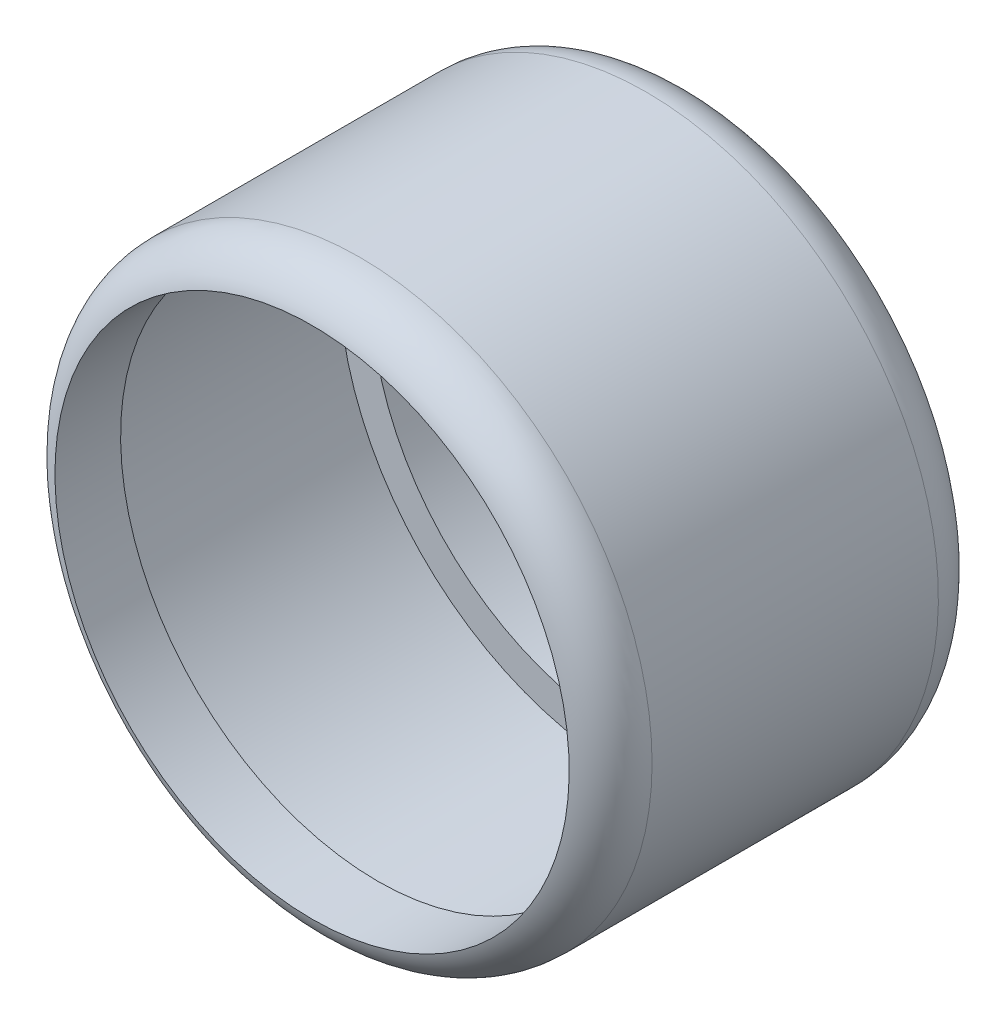
SolidWorks part; units mm, degrees
material "Silicon"
ref_plane "Front Plane" through (0, 0, 0) normal (0, 0, 1) x (1, 0, 0)
ref_plane "Top Plane" through (0, 0, 0) normal (0, 1, 0) x (1, 0, 0)
ref_plane "Right Plane" through (0, 0, 0) normal (1, 0, 0) x (0, 0, -1)
sketch "Sketch1" plane through (0, 0, 0) normal (0, 1, 0) x (1, 0, 0)
  circle A0 centre (0, 0) radius 28.9
  circle A1 centre (0, 0) radius 29.15
  dimension "D1" = 57.8
  dimension "D2" = 58.3
extrude "Boss-Extrude1" add sketch "Sketch1" along normal blind 25
sketch3d "3DSketch1"
  circle A0 centre (0, 25, 0) radius 29.15 construction
  point P0 (9.529, 25, -27.5485)
  point P3 (0, 54.15, 0)
ref_plane "Plane1" through (0, 25, 0) normal (0, 1, 0) x (1, 0, 0)
sketch "Sketch2" plane through (0, 25, 0) normal (0, 1, 0) x (1, 0, 0)
  circle A0 centre (0, 0) radius 29.15
  circle A1 centre (0, 0) radius 25.65
  dimension "D1" = 58.3
  dimension "D2" = 51.3
extrude "Boss-Extrude2" add sketch "Sketch2" along normal blind 6.55
sketch3d "3DSketch2"
  point P0 (0, 0, 0)
ref_plane "Plane2" through (0, 0, 0) normal (0, -1, 0) x (1, 0, 0)
sketch "Sketch3" plane through (0, 0, 0) normal (0, -1, 0) x (1, 0, 0)
  circle A0 centre (0, 0) radius 29.15
  circle A1 centre (0, 0) radius 25.65
  dimension "D1" = 58.3
  dimension "D2" = 51.3
extrude "Boss-Extrude3" add sketch "Sketch3" along normal blind 6.55
sketch3d "3DSketch3"
  point P0 (12.1383, -6.55, 24.583)
ref_plane "Plane3" through (0, -6.55, 0) normal (0, -1, 0) x (1, 0, 0)
sketch "Sketch4" plane through (0, -6.55, 0) normal (0, -1, 0) x (1, 0, 0)
  circle A0 centre (0, 0) radius 25.4
  circle A1 centre (0, 0) radius 24.9
  dimension "D1" = 50.8
  dimension "D2" = 49.8
extrude "Boss-Extrude4" add sketch "Sketch4" against normal blind 1
fillet "Fillet1" radius 5 2 edges at (0, -6.55, -29.15) (0, 31.55, 29.15)
move or copy body "Body-Move/Copy4" bodies to move or copy 108 109 copy no rotation origin (0, 3.225, 0) rotation axis (1, 0, 0) rotation angle 90
